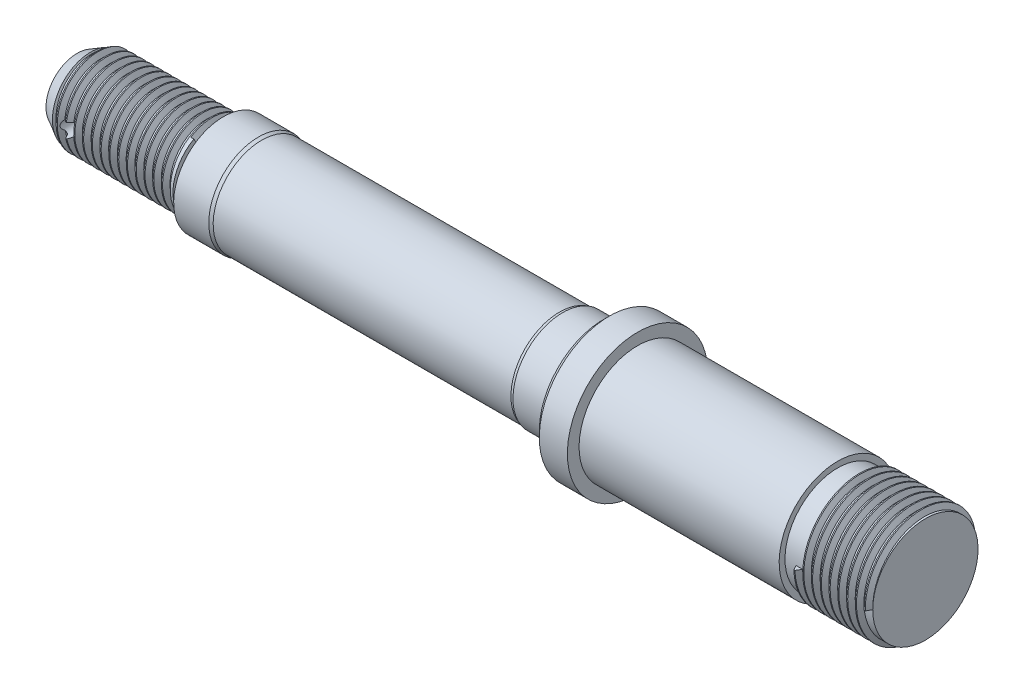
SolidWorks part; units mm, degrees
material "201 Annealed Stainless Steel (SS)"
ref_plane "Front Plane" through (0, 0, 0) normal (0, 0, 1) x (1, 0, 0)
ref_plane "Top Plane" through (0, 0, 0) normal (0, 1, 0) x (1, 0, 0)
ref_plane "Right Plane" through (0, 0, 0) normal (1, 0, 0) x (0, 0, -1)
sketch "Sketch1" plane through (0, 0, 0) normal (0, 0, 1) x (1, 0, 0)
  line L0 (34.1734, -0.0582) -> (175.1014, -0.0582) construction
  line L1 (0.1023, -0.0582) -> (0.1023, 8.4418)
  line L2 (0.1023, 8.4418) -> (6.1023, 8.4418)
  line L3 (6.1023, 8.4418) -> (6.6523, 8.2418)
  line L4 (6.6523, 8.2418) -> (57.5523, 8.2418)
  line L5 (57.5523, 8.2418) -> (58.1023, 8.4418)
  line L6 (58.1023, 8.4418) -> (65.1023, 8.4418)
  line L7 (65.1023, 8.4418) -> (65.1023, 10.9418)
  line L8 (65.1023, 10.9418) -> (66.1023, 11.9418)
  line L9 (66.1023, 11.9418) -> (70.9023, 11.9418)
  line L10 (70.9023, 11.9418) -> (70.9023, 9.9418)
  line L11 (70.9023, 9.9418) -> (105.1023, 9.9418)
  line L12 (105.1023, 9.9418) -> (105.1023, 8.9418)
  line L13 (105.1023, 8.9418) -> (108.1023, 8.9418)
  line L14 (108.1023, 8.9418) -> (120.1023, 8.9418)
  line L15 (87.4589, 9.9418) -> (93.3279, 9.9418)
  line L17 (120.1023, 8.9418) -> (120.1023, -0.0582)
  line L19 (120.1023, -0.0582) -> (34.1734, -0.0582)
  line L20 (0.1023, -0.0582) -> (27.1023, -0.0582)
  line L21 (27.1023, -0.0582) -> (34.1734, -0.0582)
  point P3 (106.6023, 8.9418)
  point P25 (65.1023, 9.6918)
  dimension "D2" = 6
  dimension "D3" = 6.55
  dimension "D4" = 8.3
  dimension "D5" = 57.45
  dimension "D6" = 58
  dimension "D7" = 8.5
  dimension "D8" = 65
  dimension "D9" = 66
  dimension "D10" = 12
  dimension "D11" = 11
  dimension "D12" = 70.8
  dimension "D13" = 8.3
  dimension "D14" = 9
  dimension "D15" = 10
  dimension "D16" = 120
  dimension "D17" = 105
  dimension "D18" = 108
  dimension "D19" = 12
  dimension "D20" = 27
  dimension "D21" = 180
  dimension "D22" = 0
revolve "Revolve1" add sketch "Sketch1" angle 360 about L0
thread "Thread1" pitch 1.5 method extrude profile "Thread Profile6" start angle 0, offset 0, length 12, pitch 1.5, diameter 18
ref_plane "Plane6" through (120.1023, -0.0582, 9) normal (0, -1, 0) x (0, 0, 1)
sketch "Thread Profile6" plane through (120.1023, -0.0582, 9) normal (0, -1, 0) x (0, 0, 1)
  line L0 (0, 0) -> (0, 1.5) construction
  line L1 (0, 0) -> (0.8119, 0.4687)
  line L2 (0.8119, 0.4687) -> (0.8119, 0.6562)
  line L3 (0.8119, 0.6562) -> (0, 1.125)
  line L4 (0.8119, 0.5625) -> (0, 0.5625) construction
  line L11 (0, 0) -> (0, 1.125)
  point P2 (0, 0)
  dimension "Pitch" = 1.5
  dimension "Profile_Angle" = 60
  dimension "Profile_Land" = 0.1875
  dimension "Profile_Height" = 0.8119
sketch "Sketch29" plane through (0, 0, 0) normal (0, 1, 0) x (1, 0, 0)
  line L4 (0, 0) -> (9.9871, 0) construction
  line L5 (3, 5.5) -> (0, 5.5)
  line L6 (3, 5.5) -> (3, -5.5)
  line L7 (0, 5.5) -> (0, -5.5)
  line L8 (3, -5.5) -> (0, -5.5)
  line L9 (3, 5.5) -> (0, -5.5) construction
  line L10 (0, 5.5) -> (3, -5.5) construction
  point P3 (1.5, 0)
  dimension "D1" = 3
  dimension "D2" = 5.5
  dimension "D3" = 5.5
sketch "Sketch30" plane through (0.1023, 0, 0) normal (-1, 0, 0) x (0, 0, 1)
  circle A0 centre (0, 0) radius 7.1438
  dimension "D1" = 14.2875
extrude "Boss-Extrude1" add sketch "Sketch30" along normal blind 25
sketch "Sketch35" plane through (0, 0, 0) normal (0, 0, 1) x (1, 0, 0)
  circle A0 centre (-19.7857, 0) radius 1.1906
  point P0 (-19.7857, 0)
  dimension "D1" = 2.3813
extrude "Cut-Extrude1" cut sketch "Sketch35" against normal through all both and the other way through all
sketch "Sketch36" plane through (0, 0, 0) normal (0, 0, 1) x (1, 0, 0)
  line L0 (0.1023, 8.4418) -> (0.1023, -8.5582) construction
  line L1 (0.1023, 3.8914) -> (-1.3775, 3.8914)
  line L2 (0.1023, 3.8914) -> (0.1023, 8.1159)
  line L3 (0.1023, 8.1159) -> (-1.3775, 8.1159)
  line L4 (-1.3775, 3.8914) -> (-1.3775, 8.1159)
revolve "Cut-Revolve1" cut sketch "Sketch36" angle 360 about L4
thread "Thread3" pitch 1.5 profile "Thread Profile9" start angle 0, offset 0, length 23, pitch 1.5, diameter 14.2875
ref_plane "Plane9" through (-24.8977, 0, -7.1438) normal (0, -1, 0) x (0, 0, -1)
sketch "Thread Profile9" plane through (-24.8977, 0, -7.1438) normal (0, -1, 0) x (0, 0, -1)
  line L0 (0, 0) -> (0, 1.5) construction
  line L11 (0, 0) -> (0, 1.3125)
  line L12 (0, 1.3125) -> (-0.8119, 0.8437)
  line L13 (-0.8119, 0.8437) -> (-0.8119, 0.4687)
  line L15 (-0.8119, 0.4687) -> (0, 0)
  line L17 (-0.8119, 0.6562) -> (0, 0.6562) construction
  point P2 (0, 0)
  dimension "Pitch" = 1.5
  dimension "Profile_Angle" = 60
  dimension "Profile_Land" = 0.375
  dimension "Profile_Height" = 0.8119
sketch "Sketch45" plane through (0, 0, 0) normal (0, 1, 0) x (1, 0, 0)
  line L0 (-29.4833, 10.1413) -> (-28.9829, 3.0448)
  line L1 (-28.9829, 3.0448) -> (-21.1585, 7.4119)
  line L2 (-21.1585, 7.4119) -> (-29.4833, 10.1413)
  point P2 (-17.8401, 2.867)
  point P4 (-11.4636, 7.7943)
  point P5 (-29.2104, 3.9546)
  point P6 (-29.4833, 10.1413)
  point P7 (-21.1585, 7.4119)
  point P8 (-28.9829, 3.0448)
revolve "Cut-Revolve2" cut sketch "Sketch45" angle 360 about L4
